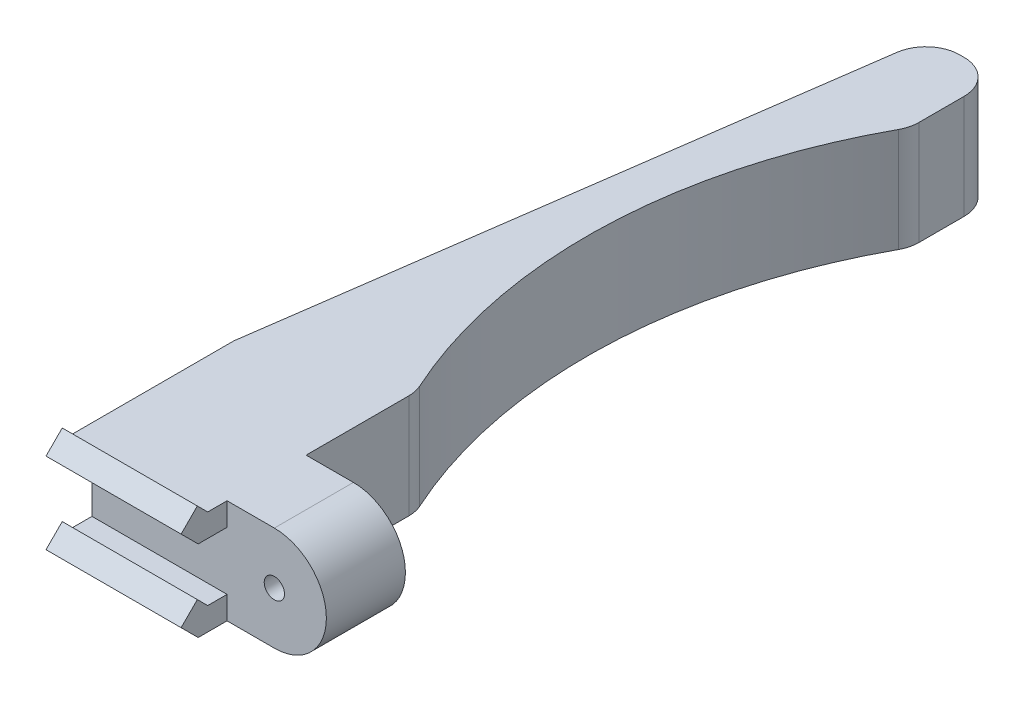
SolidWorks part; units mm, degrees
material "PVC 0.007 Plasticized"
ref_plane "Front Plane" through (0, 0, 0) normal (0, 0, 1) x (1, 0, 0)
ref_plane "Top Plane" through (0, 0, 0) normal (0, 1, 0) x (1, 0, 0)
ref_plane "Right Plane" through (0, 0, 0) normal (1, 0, 0) x (0, 0, -1)
sketch "Sketch1" plane through (0, 0, 0) normal (0, 0, 1) x (1, 0, 0)
  line L0 (0, 0) -> (0, 7.3842) construction
  line L1 (-5, -7.3842) -> (5, -7.3842)
  line L2 (-5, -7.3842) -> (-5, 7.3842)
  line L3 (-5, 7.3842) -> (5, 7.3842)
  line L4 (5, -7.3842) -> (5, 7.3842)
  line L5 (0, -7.3842) -> (0, 0) construction
  point P0 (0, -1.566)
  dimension "D1" = 10
  dimension "D2" = 14.7684
extrude "Boss-Extrude1" add sketch "Sketch1" along normal mid plane 5
sketch "Sketch2" plane through (5, 0, 0) normal (1, 0, 0) x (0, 0, -1)
  line L0 (-2.65, 4.8966) -> (-2.5, 4.8966)
  line L1 (-2.5, 4.8966) -> (-2.5, 3.1966)
  line L2 (-2.5, 3.1966) -> (-2.65, 3.1966)
  line L4 (-4.6379, 3.1966) -> (-2.65, 3.1966)
  line L5 (-2.65, 4.8966) -> (-3.9337, 4.8966)
  line L6 (-3.9337, 4.8966) -> (-4.7, 5.6629)
  line L7 (-4.7, 5.6629) -> (-5.9021, 4.4608)
  line L8 (-5.9021, 4.4608) -> (-4.6379, 3.1966)
  line L16 (-2.5, 7.3842) -> (2.5, 7.3842) construction
  line L17 (-2.5, -7.3842) -> (-2.5, 7.3842) construction
  line L18 (-2.65, -1.1034) -> (-2.5, -1.1034)
  line L19 (-2.5, -1.1034) -> (-2.5, -2.8034)
  line L20 (-2.5, -2.8034) -> (-2.65, -2.8034)
  line L21 (-4.6379, -2.8034) -> (-2.65, -2.8034)
  line L22 (-2.65, -1.1034) -> (-3.9337, -1.1034)
  line L23 (-3.9337, -1.1034) -> (-4.7, -0.3371)
  line L24 (-4.7, -0.3371) -> (-5.9021, -1.5392)
  line L25 (-5.9021, -1.5392) -> (-4.6379, -2.8034)
  dimension "D2" = 135
  dimension "D3" = 1.7
  dimension "D4" = 1.9879
  dimension "D5" = 1.7879
  dimension "D6" = 1.7
  dimension "D7" = 1.2837
  dimension "D8" = 0.15
  dimension "D9" = 1.0837
  dimension "D10" = 0.15
  dimension "D11" = 2.4876
  dimension "D12" = 2
extrude "Boss-Extrude2" add sketch "Sketch2" against normal up to surface (10 mm away) up to face at (-5, 0, 0)
sketch "Sketch3" plane through (5, 0, 0) normal (1, 0, 0) x (0, 0, -1)
  line L0 (2.5, -7.3842) -> (2.5, 7.3842) construction
  line L1 (-2.5, 7.3842) -> (2.5, 7.3842)
  line L2 (-2.5, 7.3842) -> (-2.5, 4.8966)
  line L3 (-2.5, 4.8966) -> (2.5, 4.8966)
  line L4 (2.5, 7.3842) -> (2.5, 4.8966)
  line L5 (-2.5, -7.3842) -> (-2.5, -2.8034) construction
  line L6 (-2.5, 4.8966) -> (-3.9337, 4.8966) construction
  line L7 (-2.5, -2.8034) -> (2.5, -2.8034)
  line L8 (-2.5, -2.8034) -> (-2.5, -7.3842)
  line L9 (-2.5, -7.3842) -> (2.5, -7.3842)
  line L10 (2.5, -2.8034) -> (2.5, -7.3842)
  dimension "D1" = 4.5808
extrude "Cut-Extrude1" cut sketch "Sketch3" against normal up to next
sketch "Sketch5" plane through (0, -2.8034, 0) normal (0, -1, 0) x (1, 0, 0)
  line L0 (-5, -2.5) -> (-5, -8)
  line L1 (-5, -8) -> (1.3524, -53.2)
  line L2 (1.3524, -53.2) -> (6.3524, -53.2)
  line L3 (-5, -2.5) -> (5, -2.5)
  line L4 (6.3524, -53.2) -> (6.3524, -46.7)
  line L5 (5, -2.5) -> (5, -11.5)
  line L6 (-5, -2.5) -> (5, -2.5) construction
  arc A0 (5, -11.5) -> (6.3524, -46.7) centre (39.6089, -27.7962) ccw
  dimension "D7" = 38.2537
  dimension "D1" = 172
  dimension "D2" = 45.2
  dimension "D3" = 5
  dimension "D4" = 6.5
  dimension "D5" = 5.5
  dimension "D6" = 9
  dimension "D9" = 90
  dimension "D10" = 90
extrude "Boss-Extrude3" add sketch "Sketch5" against normal up to surface (7.7 mm away) up to face at (0, 4.8966, 0.7169)
sketch "Sketch6" plane through (0, 0, 2.5) normal (0, 0, 1) x (1, 0, 0)
  line L0 (5, 4.8966) -> (8.5, 4.8966)
  line L1 (8.5, -2.8034) -> (5, -2.8034)
  line L2 (5, -2.8034) -> (5, 4.8966)
  line L3 (5, 4.8966) -> (5, -2.8034) construction
  arc A0 (8.5, 4.8966) -> (8.5, -2.8034) centre (8.5, 1.0466) cw
  circle A1 centre (8.5, 1.0466) radius 0.75
  dimension "D1" = 1.5
  dimension "D3" = 3.85
  dimension "D2" = 3.5
extrude "Boss-Extrude4" add sketch "Sketch6" against normal blind 5.85
fillet "Fillet1" radius 2.5 4 edges at (1.3524, 1.0466, -53.2) (6.3524, 1.0466, -53.2) (6.3524, 1.0466, -46.7) (5, 1.0466, -11.5)
